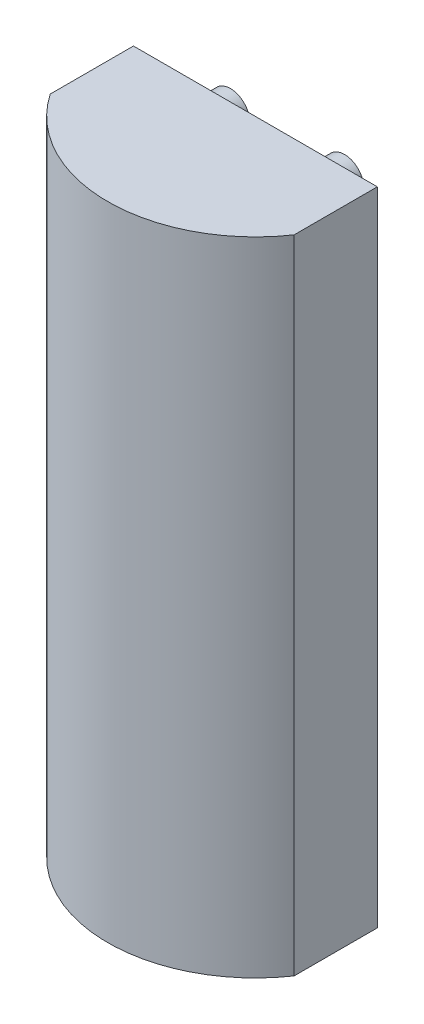
SolidWorks part; units mm, degrees
material "ABS"
ref_plane "Спереди" through (0, 0, 0) normal (0, 0, 1) x (1, 0, 0)
ref_plane "Сверху" through (0, 0, 0) normal (0, 1, 0) x (1, 0, 0)
ref_plane "Справа" through (0, 0, 0) normal (1, 0, 0) x (0, 0, -1)
sketch "Эскиз1" plane through (0, 0, 0) normal (0, 1, 0) x (1, 0, 0)
  line L0 (-23, 0) -> (23, 0)
  arc A0 (-23, 0) -> (23, 0) centre (0, 0) ccw
  dimension "D1" = 23
extrude "Бобышка-Вытянуть1" add sketch "Эскиз1" along normal blind 100
sketch "Эскиз2" plane through (0, 0, 0) normal (0, 0, -1) x (-1, 0, 0)
  line L0 (0, 100) -> (0, 0) construction
  line L1 (-23, 100) -> (23, 100) construction
  line L2 (-23, 50) -> (5.22, 50) construction
  line L3 (-23, 100) -> (-23, 0) construction
  line L4 (-8.89, 93.815) -> (8.89, 93.815) construction
  line L5 (-8.89, 93.815) -> (-8.89, 6.185) construction
  circle A0 centre (-8.89, 93.815) radius 3
  circle A1 centre (8.89, 93.815) radius 3
  circle A2 centre (-8.89, 6.185) radius 3
  circle A3 centre (8.89, 6.185) radius 3
  circle A4 centre (-8.89, 93.815) radius 0.9
  circle A5 centre (8.89, 93.815) radius 0.9
  circle A6 centre (8.89, 6.185) radius 0.9
  circle A7 centre (-8.89, 6.185) radius 0.9
  point P17 (0, 93.815)
  point P19 (-8.89, 50)
  dimension "D1" = 6
  dimension "D4" = 1.8
  dimension "D2" = 2
  dimension "D3" = 2
extrude "Бобышка-Вытянуть2" add sketch "Эскиз2" along normal blind 5
sketch "Эскиз4" plane through (0, 0, 0) normal (0, 0, -1) x (-1, 0, 0)
  line L0 (-23, 0) -> (23, 0) construction
  line L1 (-19, 0) -> (19, 0)
  line L2 (-19, 0) -> (-19, 100)
  line L3 (-19, 100) -> (19, 100)
  line L4 (19, 0) -> (19, 100)
  line L5 (-23, 100) -> (23, 100) construction
  line L7 (-33.2966, 110.6364) -> (33.2966, 110.6364)
  line L8 (-33.2966, 110.6364) -> (-33.2966, -11.5529)
  line L9 (-33.2966, -11.5529) -> (33.2966, -11.5529)
  line L10 (33.2966, 110.6364) -> (33.2966, -11.5529)
  line L11 (-33.2966, 110.6364) -> (33.2966, -11.5529) construction
  line L12 (-33.2966, -11.5529) -> (33.2966, 110.6364) construction
  point P8 (0, 0)
  point P10 (0, 49.5418)
  dimension "D1" = 38
extrude "Вырез-Вытянуть1" cut sketch "Эскиз4" against normal through all
